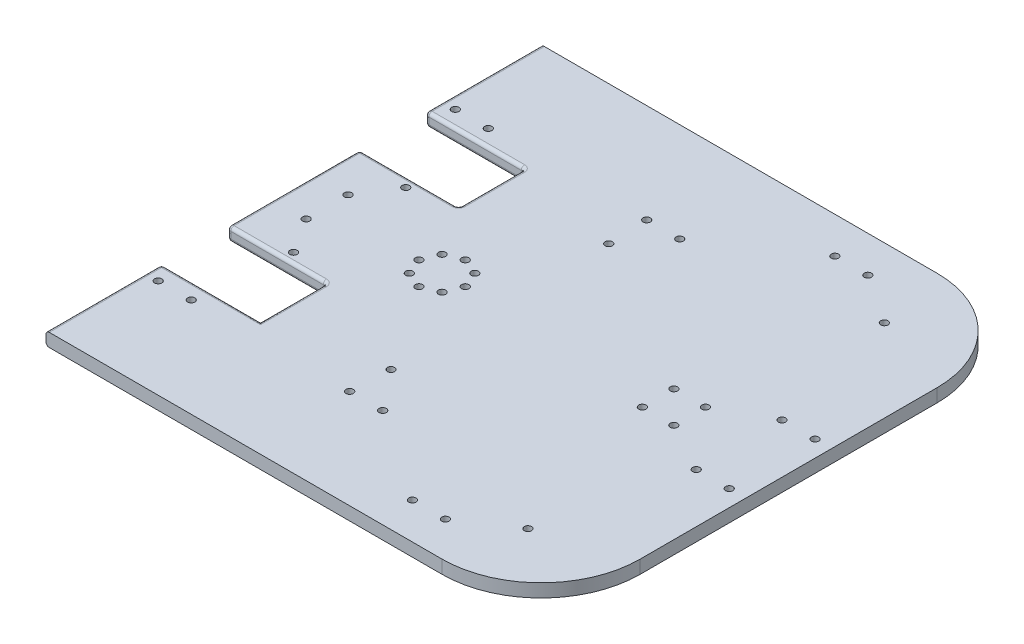
SolidWorks part; units mm, degrees
ref_plane "前视基准面" through (0, 0, 0) normal (0, 0, 1) x (1, 0, 0)
ref_plane "上视基准面" through (0, 0, 0) normal (0, 1, 0) x (1, 0, 0)
ref_plane "右视基准面" through (0, 0, 0) normal (1, 0, 0) x (0, 0, -1)
other "Configuration Table"
sketch "草图1" plane through (0, 0, 0) normal (0, 1, 0) x (1, 0, 0)
  line L1 (-150, 75) -> (150, 75)
  line L2 (-150, 75) -> (-150, -75)
  line L3 (-150, -75) -> (150, -75)
  line L4 (150, 75) -> (150, -75)
  dimension "D1" = 150
  dimension "D2" = 150
  dimension "D3" = 300
  dimension "D4" = 75
extrude "凸台-拉伸1" add sketch "草图1" along normal blind 4
fillet "圆角4" radius 30 1 edges at (-150, 2, 75) type face fillet first side face at (-150, 2, 0) second side face at (0, 2, 75)
fillet "圆角5" radius 30 1 edges at (-150, 2, -75) type face fillet first side face at (-150, 2, -15) second side face at (0, 2, -75)
fillet "圆角6" radius 30 1 edges at (150, 2, -75) type face fillet first side face at (15, 2, -75) second side face at (150, 2, 0)
fillet "圆角7" radius 30 1 edges at (150, 2, 75) type face fillet first side face at (150, 2, 15) second side face at (15, 2, 75)
sketch "草图2" plane through (0, 0, 0) normal (0, -1, 0) x (1, 0, 0)
  line L0 (0, 0) -> (-45, 0)
  line L1 (2.2, 0) -> (-2.2, 0) construction
  line L3 (0, -2.2) -> (0, 2.2) construction
  point P5 (-45, 7.02)
  dimension "D1" = 45
  dimension "D2" = 45
  dimension "D3" = 7.02
hole_wizard "Ø2.2 (2.2) 直径孔1" positions "草图3" profile "草图4" hole size "Ø2.2" standard "ANSI Metric" end condition up to next
sketch "草图3" plane through (0, 0, 0) normal (0, -1, 0) x (-1, 0, 0)
  point P0 (45, -7.02)
sketch "草图4" plane through (-45, 0, 7.02) normal (1, 0, 0) x (0, 0, -1)
  line L0 (0, 0) -> (0, 4)
  line L1 (0, 4) -> (1.1, 4)
  line L2 (1.1, 4) -> (1.1, 0)
  line L5 (1.1, 0) -> (0, 0)
  line L11 (0, -6.35) -> (0, 107.95) construction
  dimension "通孔孔直径" = 2.2
  dimension "通孔孔深度" = 4
ref_axis "基准轴1" through (-45, 0, 0) along (0, -1, 0)
pattern_circular "阵列(圆周)1" count 8 over 360 about axis through (-45, 0, 0) along (0, -1, 0) of "Ø2.2 (2.2) 直径孔1" reverse direction yes
mirror "镜向1" about plane through (0, 0, 0) normal (1, 0, 0) of "阵列(圆周)1", "Ø2.2 (2.2) 直径孔1"
sketch "草图5" plane through (0, 0, 0) normal (0, -1, 0) x (1, 0, 0)
  line L0 (-150, -45) -> (-150, 45) construction
  line L1 (2.2, 0) -> (-2.2, 0) construction
  point P0 (-120, 4.775)
  point P1 (-120, -4.78)
  point P6 (-110.45, -4.78)
  point P7 (-110.45, 4.775)
  dimension "D1" = 30
  dimension "D2" = 4.775
  dimension "D3" = 4.78
  dimension "D4" = 30
  dimension "D5" = 9.55
  dimension "D6" = 4.78
  dimension "D7" = 4.775
  dimension "D8" = 9.55
hole_wizard "Ø2.2 (2.2) 直径孔2" positions "草图6" profile "草图7" hole size "Ø2.2" standard "ANSI Metric" end condition up to next
sketch "草图6" plane through (0, 0, 0) normal (0, -1, 0) x (-1, 0, 0)
  point P0 (120, 4.78)
  point P3 (120, -4.775)
  point P6 (110.45, -4.775)
  point P9 (110.45, 4.78)
sketch "草图7" plane through (-120, 0, -4.78) normal (1, 0, 0) x (0, 0, -1)
  line L0 (0, 0) -> (0, 4)
  line L1 (0, 4) -> (1.1, 4)
  line L2 (1.1, 4) -> (1.1, 0)
  line L5 (1.1, 0) -> (0, 0)
  line L11 (0, -6.35) -> (0, 107.95) construction
  dimension "通孔孔直径" = 2.2
  dimension "通孔孔深度" = 4
mirror "镜向2" about plane through (0, 0, 0) normal (1, 0, 0) of "Ø2.2 (2.2) 直径孔2"
sketch "草图8" plane through (0, 4, 0) normal (0, 1, 0) x (1, 0, 0)
  line L0 (0, -2.2) -> (0, 2.2) construction
  line L1 (0, 0) -> (-45, 0) construction
  line L2 (-2.2, 0) -> (2.2, 0) construction
  point P0 (-30, 18)
  point P1 (-40, 18)
  point P2 (-40, -18)
  point P3 (-30, -18)
  dimension "D1" = 30
  dimension "D2" = 18
  dimension "D3" = 40
  dimension "D4" = 18
  dimension "D5" = 18
  dimension "D6" = 40
  dimension "D7" = 30
  dimension "D8" = 18
hole_wizard "Ø2.2 (2.2) 直径孔4" positions "草图13" profile "草图14" hole size "Ø2.2" standard "ANSI Metric" end condition up to next
sketch "草图13" plane through (0, 4, 0) normal (0, 1, 0) x (1, 0, 0)
  line L0 (-120, -75) -> (120, -75) construction
  line L1 (0, -2.2) -> (0, 2.2) construction
  point P0 (100, -64)
  point P2 (110, -64)
  point P4 (-100, -64)
  point P6 (-110, -64)
  dimension "D1" = 11
  dimension "D2" = 11
  dimension "D3" = 11
  dimension "D4" = 11
  dimension "D5" = 110
  dimension "D6" = 100
  dimension "D7" = 110
  dimension "D8" = 100
sketch "草图14" plane through (100, 4, 64) normal (1, 0, 0) x (0, 0, 1)
  line L0 (0, 0) -> (0, 4)
  line L1 (0, 4) -> (1.1, 4)
  line L2 (1.1, 4) -> (1.1, 0)
  line L5 (1.1, 0) -> (0, 0)
  line L11 (0, -6.35) -> (0, 107.95) construction
  dimension "通孔孔直径" = 2.2
  dimension "通孔孔深度" = 4
mirror "镜向4" about plane through (0, 0, 0) normal (0, 0, 1) of "Ø2.2 (2.2) 直径孔4"
hole_wizard "Ø2.2 (2.2) Diameter Hole1" positions "草图15" profile "草图16" hole size "Ø2.2" standard "ANSI Metric" end condition up to next
sketch "草图15" plane through (0, 4, 0) normal (0, 1, 0) x (1, 0, 0)
  line L0 (0, -2.2) -> (0, 2.2) construction
  line L1 (-2.2, 0) -> (2.2, 0) construction
  point P0 (-125, 54)
  dimension "D1" = 125
  dimension "D2" = 54
sketch "草图16" plane through (-125, 4, -54) normal (1, 0, 0) x (0, 0, 1)
  line L0 (0, 0) -> (0, 4)
  line L1 (0, 4) -> (1.1, 4)
  line L2 (1.1, 4) -> (1.1, 0)
  line L5 (1.1, 0) -> (0, 0)
  line L11 (0, -6.35) -> (0, 107.95) construction
  dimension "通孔孔直径" = 2.2
  dimension "通孔孔深度" = 4
mirror "镜向5" about plane through (0, 0, 0) normal (1, 0, 0) of "Ø2.2 (2.2) Diameter Hole1" second plane through (0, 0, 0) second plane normal (0, 0, 1)
hole_wizard "Ø2.2 (2.2) 直径孔6" positions "草图17" profile "草图18" hole size "Ø2.2" standard "ANSI Metric" end condition up to next
sketch "草图17" plane through (0, 4, 0) normal (0, 1, 0) x (1, 0, 0)
  line L0 (0, -2.2) -> (0, 2.2) construction
  line L1 (-2.2, 0) -> (2.2, 0) construction
  point P0 (-62.5, 33)
  point P13 (-62.5, -33)
  point P14 (62.5, -33)
  point P15 (62.5, 33)
  dimension "D1" = 62.5
  dimension "D2" = 33
sketch "草图18" plane through (-62.5, 4, -33) normal (1, 0, 0) x (0, 0, 1)
  line L0 (0, 0) -> (0, 4)
  line L1 (0, 4) -> (1.1, 4)
  line L2 (1.1, 4) -> (1.1, 0)
  line L5 (1.1, 0) -> (0, 0)
  line L11 (0, -6.35) -> (0, 107.95) construction
  dimension "通孔孔直径" = 2.2
  dimension "通孔孔深度" = 4
sketch "草图19" plane through (0, 4, 0) normal (0, 1, 0) x (1, 0, 0)
  line L0 (-150, 45) -> (-150, -45) construction
  point P0 (-145, 13)
  point P2 (-135, 13)
  dimension "D1" = 5
  dimension "D2" = 10
  dimension "D3" = 13
  dimension "D4" = 13
hole_wizard "Ø2.2 (2.2) Diameter Hole2" positions "草图19" profile "草图20" hole size "Ø2.2" standard "ANSI Metric" end condition up to next
sketch "草图20" plane through (-145, 4, -13) normal (1, 0, 0) x (0, 0, 1)
  line L0 (0, 0) -> (0, 4)
  line L1 (0, 4) -> (1.1, 4)
  line L2 (1.1, 4) -> (1.1, 0)
  line L5 (1.1, 0) -> (0, 0)
  line L11 (0, -6.35) -> (0, 107.95) construction
  dimension "Thru Hole Dia." = 2.2
  dimension "Thru Hole Depth" = 4
mirror "镜向6" about plane through (0, 0, 0) normal (1, 0, 0) of "Ø2.2 (2.2) Diameter Hole2" second plane through (0, 0, 0) second plane normal (0, 0, 1)
sketch "草图21" plane through (0, 4, 0) normal (0, 1, 0) x (1, 0, 0)
  line L0 (-2.2, 0) -> (2.2, 0) construction
  line L1 (-150, 45) -> (-150, -45) construction
  line L2 (150, -45) -> (150, 45) construction
  point P0 (-80, 45)
  point P2 (-70, 45)
  point P4 (-46, 45)
  point P6 (-36, 45)
  point P8 (4, 45)
  point P10 (14, 45)
  point P23 (62, 45)
  point P25 (72, 45)
  dimension "D1" = 45
  dimension "D2" = 45
  dimension "D3" = 45
  dimension "D4" = 45
  dimension "D5" = 10
  dimension "D6" = 10
  dimension "D7" = 70
  dimension "D8" = 34
  dimension "D9" = 45
  dimension "D10" = 45
  dimension "D11" = 10
  dimension "D12" = 45
  dimension "D13" = 45
  dimension "D14" = 58
  dimension "D15" = 78
  dimension "D16" = 10
hole_wizard "Ø2.2 (2.2) Diameter Hole3" positions "草图21" profile "草图22" hole size "Ø2.2" standard "ANSI Metric" end condition up to next
sketch "草图22" plane through (-80, 4, -45) normal (1, 0, 0) x (0, 0, 1)
  line L0 (0, 0) -> (0, 4)
  line L1 (0, 4) -> (1.1, 4)
  line L2 (1.1, 4) -> (1.1, 0)
  line L5 (1.1, 0) -> (0, 0)
  line L11 (0, -6.35) -> (0, 107.95) construction
  dimension "Thru Hole Dia." = 2.2
  dimension "Thru Hole Depth" = 4
mirror "镜向7" about plane through (0, 0, 0) normal (0, 0, 1) of "Ø2.2 (2.2) Diameter Hole3"
sketch "草图23" plane through (0, 0, 0) normal (0, -1, 0) x (1, 0, 0)
  line L0 (0, -2.2) -> (0, 2.2) construction
  line L1 (2.2, 0) -> (-2.2, 0) construction
  point P0 (-10.16, 6.35)
  dimension "D1" = 10.16
  dimension "D2" = 6.35
hole_wizard "Ø2.2 (2.2) Diameter Hole4" positions "草图23" profile "草图24" hole size "Ø2.2" standard "ANSI Metric" end condition up to next
sketch "草图24" plane through (-10.16, 0, 6.35) normal (1, 0, 0) x (0, 0, -1)
  line L0 (0, 0) -> (0, 4)
  line L1 (0, 4) -> (1.1, 4)
  line L2 (1.1, 4) -> (1.1, 0)
  line L5 (1.1, 0) -> (0, 0)
  line L11 (0, -6.35) -> (0, 107.95) construction
  dimension "Thru Hole Dia." = 2.2
  dimension "Thru Hole Depth" = 4
mirror "镜向8" about plane through (0, 0, 0) normal (0, 0, 1) of "Ø2.2 (2.2) Diameter Hole4" second plane through (0, 0, 0) second plane normal (1, 0, 0)
sketch "草图25" plane through (0, 0, 0) normal (0, 0, 1) x (1, 0, 0)
  line L0 (-120, 4) -> (120, 4) construction
  line L2 (0, 4) -> (0, 0)
  line L5 (0, 4) -> (-150, 4)
  line L6 (-150, 4) -> (-150, 0)
  line L7 (-150, 0) -> (-150, 4) construction
  line L8 (-150, 0) -> (0, 0)
sketch "草图26" plane through (0, 4, 0) normal (0, 1, 0) x (1, 0, 0)
  line L0 (-2.2, 0) -> (2.2, 0) construction
  line L1 (0, -2.2) -> (0, 2.2) construction
  point P0 (-17, 17)
  dimension "D1" = 17
  dimension "D2" = 17
hole_wizard "Ø2.2 (2.2) Diameter Hole5" positions "草图26" profile "草图27" hole size "Ø2.2" standard "ANSI Metric" end condition up to next
sketch "草图27" plane through (-17, 4, -17) normal (1, 0, 0) x (0, 0, 1)
  line L0 (0, 0) -> (0, 4)
  line L1 (0, 4) -> (1.1, 4)
  line L2 (1.1, 4) -> (1.1, 0)
  line L5 (1.1, 0) -> (0, 0)
  line L11 (0, -6.35) -> (0, 107.95) construction
  dimension "Thru Hole Dia." = 2.2
  dimension "Thru Hole Depth" = 4
mirror "镜向9" about plane through (0, 0, 0) normal (0, 0, 1) of "Ø2.2 (2.2) Diameter Hole5" second plane through (0, 0, 0) second plane normal (1, 0, 0)
extrude "切除-拉伸3" cut sketch "草图25" against normal through all both and the other way through all
sketch "草图28" plane through (0, 4, 0) normal (0, 1, 0) x (1, 0, 0)
  line L0 (0, 75) -> (0, -75) construction
  line L1 (30, 20) -> (0, 20)
  line L2 (30, 20) -> (30, 40)
  line L3 (30, 40) -> (0, 40)
  line L4 (0, 20) -> (0, 40)
  line L5 (120, 75) -> (0, 75) construction
  dimension "D1" = 20
  dimension "D2" = 35
  dimension "D3" = 30
extrude "切除-拉伸4" cut sketch "草图28" against normal through all
mirror "镜向10" about plane through (0, 0, 0) normal (0, 0, 1) of "切除-拉伸4"
fillet "圆角8" radius 1 25 edges at (15, 0, 40) (15, 4, 40) (0, 2, 40) (0, 0, 57.5) (0, 4, 57.5) (30, 2, 20) (30, 0, 30) (30, 4, 30) (0, 0, 0) (0, 4, 0) (15, 0, 20) (15, 4, 20) (0, 2, 20) (0, 2, -20) (15, 0, -20) (15, 4, -20) (30, 2, -20) (30, 2, -40) (30, 0, -30) (30, 4, -30) (0, 0, -57.5) (0, 4, -57.5) (0, 2, -40) (15, 0, -40) (15, 4, -40)
